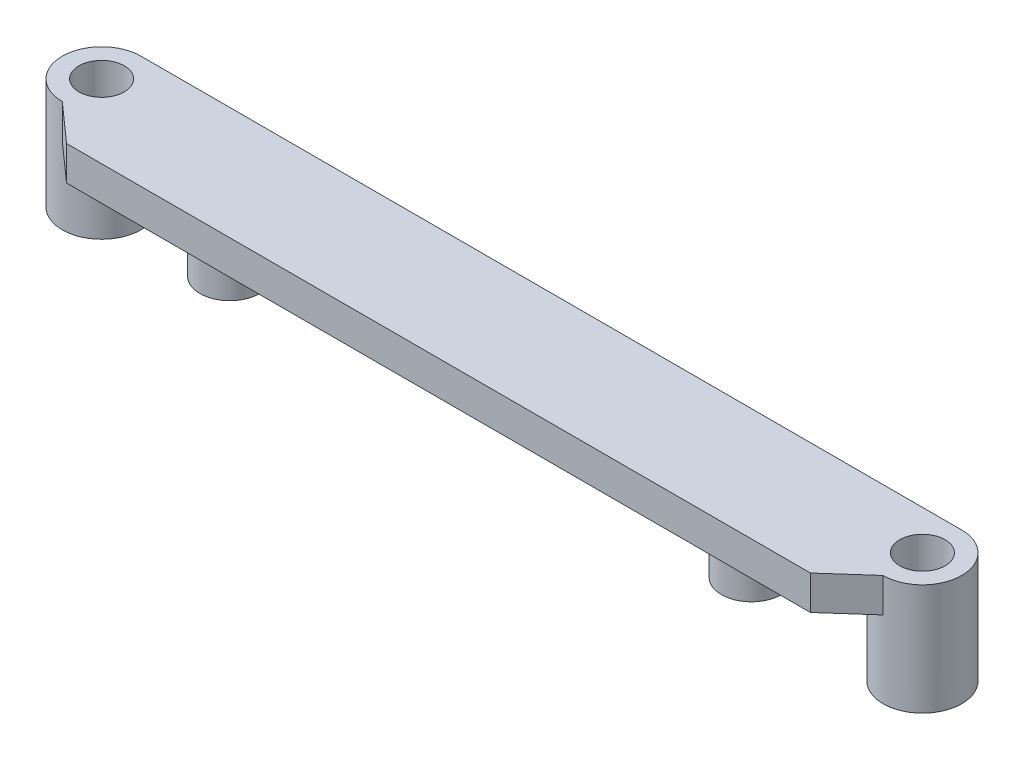
SolidWorks part; units mm, degrees
ref_plane "Front Plane" through (0, 0, 0) normal (0, 0, 1) x (1, 0, 0)
ref_plane "Top Plane" through (0, 0, 0) normal (0, 1, 0) x (1, 0, 0)
ref_plane "Right Plane" through (0, 0, 0) normal (1, 0, 0) x (0, 0, -1)
sketch "Sketch1" plane through (0, 0, 0) normal (0, 1, 0) x (1, 0, 0)
  line L0 (0, 16.5) -> (0, -16.5) construction
  line L1 (-24, -16.5) -> (24, -16.5) construction
  line L2 (-24, -16.5) -> (-24, 16.5) construction
  line L3 (-24, 16.5) -> (24, 16.5) construction
  line L4 (24, -16.5) -> (24, 16.5) construction
  line L5 (-24, -16.5) -> (24, 16.5) construction
  line L6 (-24, 16.5) -> (24, -16.5) construction
  line L7 (-24, 0) -> (24, 0) construction
  circle A0 centre (-24, 16.5) radius 1.325
  circle A1 centre (24, 16.5) radius 1.325
  circle A2 centre (-24, -16.5) radius 1.325
  circle A3 centre (24, -16.5) radius 1.325
  point P0 (0, 0)
  dimension "D3" = 2.65
  dimension "D1" = 48
  dimension "D2" = 33
sketch "Sketch2" plane through (0, 0, 0) normal (0, 1, 0) x (1, 0, 0)
  line L1 (-15.25, -15.25) -> (15.25, -15.25) construction
  line L2 (-15.25, -15.25) -> (-15.25, 15.25) construction
  line L3 (-15.25, 15.25) -> (15.25, 15.25) construction
  line L4 (15.25, -15.25) -> (15.25, 15.25) construction
  line L5 (-15.25, -15.25) -> (15.25, 15.25) construction
  line L6 (-15.25, 15.25) -> (15.25, -15.25) construction
  circle A0 centre (-15.25, 15.25) radius 2
  circle A2 centre (15.25, 15.25) radius 2
  circle A3 centre (15.25, -15.25) radius 2
  circle A4 centre (-15.25, -15.25) radius 2
  point P0 (0, 0)
  point P16 (0, 0)
  dimension "D2" = 4
  dimension "D1" = 30.5
  dimension "D3" = 4
sketch "Sketch5" plane through (0, 0, 0) normal (0, 1, 0) x (1, 0, 0)
  line L0 (-24, 14.2) -> (-21.75, 12.2)
  line L1 (24, 14.2) -> (21.75, 12.2)
  line L5 (21.75, 12.2) -> (-21.75, 12.2)
  line L6 (-24, 18.8) -> (24, 18.8)
  arc A0 (-24, 18.8) -> (-24, 14.2) centre (-24, 16.5) ccw
  arc A1 (24, 14.2) -> (24, 18.8) centre (24, 16.5) ccw
  circle A2 centre (15.25, 15.25) radius 2 construction
  dimension "D1" = 3.05
  dimension "D2" = 2
  dimension "D3" = 2.25
extrude "Boss-Extrude1" add sketch "Sketch5" along normal blind 2
sketch "Sketch6" plane through (0, 0, 0) normal (0, -1, 0) x (1, 0, 0)
  circle A2 centre (-24, -16.5) radius 2.3
  circle A3 centre (24, -16.5) radius 2.3
  dimension "D2" = 4.6
extrude "Boss-Extrude2" add sketch "Sketch6" along normal blind 4.5
extrude "Cut-Extrude1" cut sketch "Sketch1" against normal through all both and the other way through all
sketch "Sketch7" plane through (0, 0, 0) normal (0, -1, 0) x (1, 0, 0)
  circle A0 centre (-15.25, -15.25) radius 1.75
  circle A1 centre (15.25, -15.25) radius 1.75
  dimension "D1" = 3.5
extrude "Boss-Extrude3" add sketch "Sketch7" along normal blind 3
